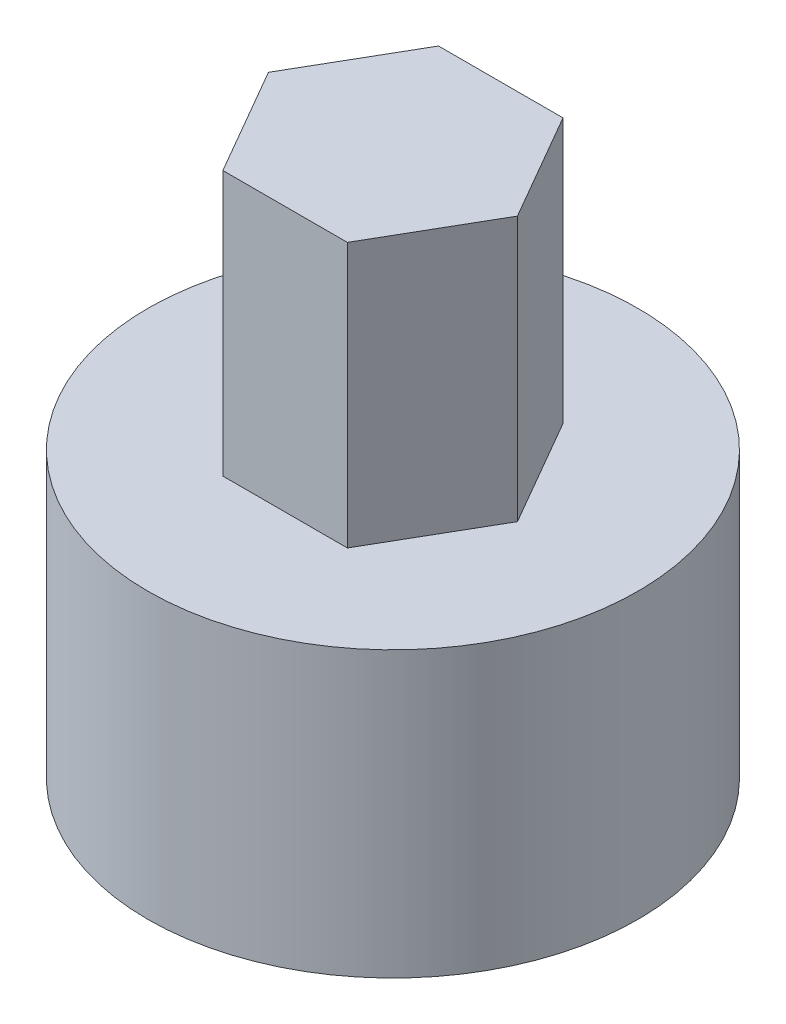
SolidWorks part; units mm, degrees
ref_plane "前视基准面" through (0, 0, 0) normal (0, 0, 1) x (1, 0, 0)
ref_plane "上视基准面" through (0, 0, 0) normal (0, 1, 0) x (1, 0, 0)
ref_plane "右视基准面" through (0, 0, 0) normal (1, 0, 0) x (0, 0, -1)
other "Configuration Table"
sketch "草图1" plane through (0, 0, 0) normal (0, 1, 0) x (1, 0, 0)
  line L0 (1, 1.3124) -> (1, -1.3124)
  line L1 (1.2702, 0) -> (0.6351, 1.1)
  line L2 (0.6351, 1.1) -> (-0.6351, 1.1)
  line L3 (-0.6351, 1.1) -> (-1.2702, 0)
  line L4 (-1.2702, 0) -> (-0.6351, -1.1)
  line L5 (-0.6351, -1.1) -> (0.6351, -1.1)
  line L6 (0.6351, -1.1) -> (1.2702, 0)
  circle A0 centre (0, 0) radius 1.1 construction
  circle A1 centre (0, 0) radius 2.5
  circle A2 centre (0, 0) radius 1.65
  dimension "D1" = 2.2
  dimension "D2" = 5
  dimension "D3" = 3.3
  dimension "D4" = 1
extrude "凸台-拉伸1" add sketch "草图1" along normal blind 2.7 contours L4 L5 L6 L1 L2 L3
extrude "凸台-拉伸3" add sketch "草图1<4>" against normal blind 0.9 contours A1
sketch "草图1<4>" plane through (0, 0, 0) normal (0, 1, 0) x (1, 0, 0) same geometry as "草图1"
extrude "凸台-拉伸2" add sketch "草图1<3>" against normal blind 2 from surface contours A1 A2 | L0 A2 L1 L6 | L0 L6 L1 region at (1.2857, 0, 0) region at (1.0901, 0, 0) region at (-2.4293, 0, 0) starting at face at (0, -0.9, 2.5)
sketch "草图1<3>" plane through (0, 0, 0) normal (0, 1, 0) x (1, 0, 0) same geometry as "草图1"
